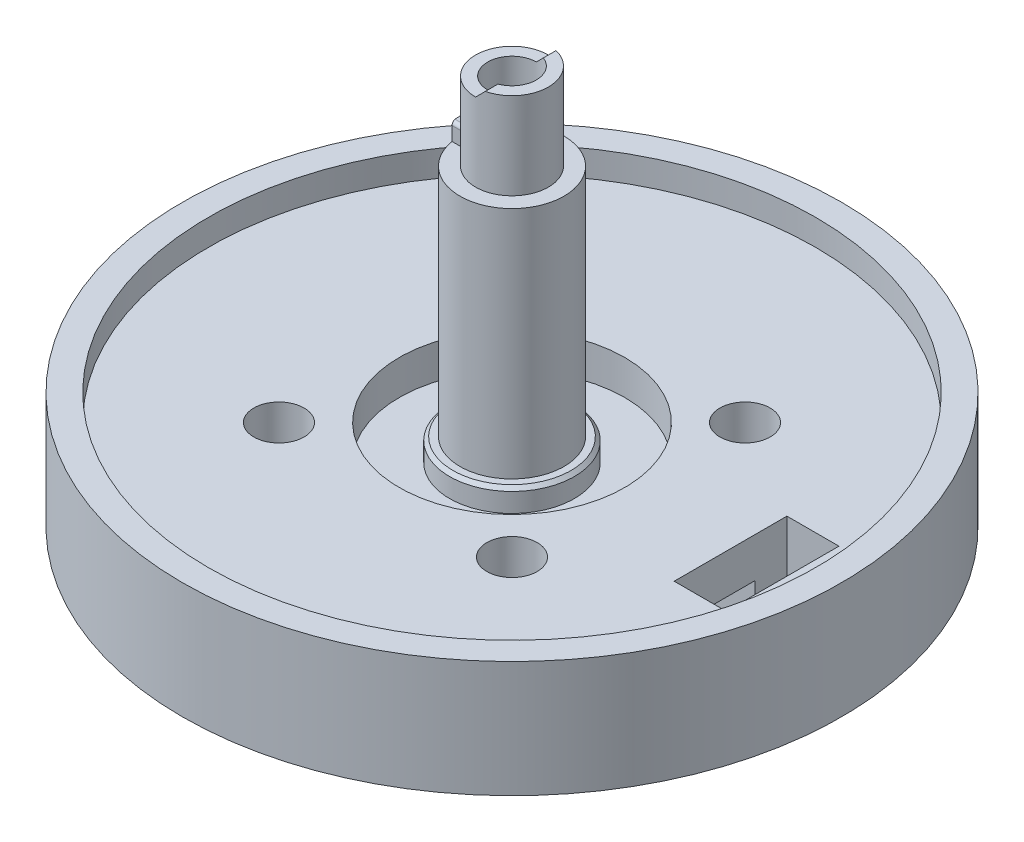
SolidWorks part; units mm, degrees
ref_plane "前视基准面" through (0, 0, 0) normal (0, 0, 1) x (1, 0, 0)
ref_plane "上视基准面" through (0, 0, 0) normal (0, 1, 0) x (1, 0, 0)
ref_plane "右视基准面" through (0, 0, 0) normal (1, 0, 0) x (0, 0, -1)
sketch "草图1" plane through (0, 0, 0) normal (0, 0, 1) x (1, 0, 0)
  line L0 (0, 0) -> (0, 22.2201) construction
  line L1 (-3, 12.8) -> (-2.1, 12.8)
  line L2 (-2.1, 12.8) -> (-2.1, 17.8)
  line L3 (-2.1, 17.8) -> (-1.4, 17.8)
  line L4 (-1.4, 17.8) -> (-1.4, -2.6859)
  line L6 (-3, -0.7) -> (-3, 12.8)
  line L7 (-19, 1.5) -> (-17.5, 1.5)
  line L8 (-17.5, 1.5) -> (-17.5, 0)
  line L9 (-17.5, 0) -> (-6.5, 0)
  line L10 (-6.5, 0) -> (-6.5, -2)
  line L13 (-19, 1.5) -> (-19, -5.2)
  line L14 (-19, -5.2) -> (-1.4, -5.2)
  line L15 (-1.4, -5.2) -> (-1.4, -2.6859)
  line L16 (-21.0007, 0) -> (21.0007, 0) construction
  line L18 (0, 0) -> (0, -7.9329) construction
  line L19 (-3, -0.7) -> (-3.6, -0.7)
  line L20 (-3.6, -0.7) -> (-3.6, -2)
  line L21 (-3.6, -2) -> (-6.5, -2)
  point P19 (0, 0)
  point P24 (-2.55, 12.8)
  dimension "D1" = 6
  dimension "D2" = 2.8
  dimension "D3" = 5
  dimension "D4" = 35
  dimension "D5" = 13
  dimension "D6" = 2
  dimension "D7" = 5.2
  dimension "D8" = 1.5
  dimension "D9" = 0.7
  dimension "D10" = 12.8
  dimension "D11" = 1.5
  dimension "D12" = 1.3
  dimension "D13" = 7.2
revolve "旋转3" add sketch "草图1" angle 360 about L0
sketch "草图3" plane through (0, 17.8, 0) normal (0, 1, 0) x (1, 0, 0)
  line L0 (0, 0) -> (-3.9693, 0) construction
  line L2 (-3.2821, 0.5) -> (-1, 0.5)
  line L3 (-3.2821, 0.5) -> (-3.2821, -0.5)
  line L4 (-3.2821, -0.5) -> (-1, -0.5)
  line L5 (-1, 0.5) -> (-1, -0.5)
  circle A1 centre (0, 0) radius 3
  circle A2 centre (0, 0) radius 3
  circle M6 centre (0, 0) radius 2.1
  dimension "D1" = 1
  dimension "D2" = 2.2821
  dimension "D3" = 1
  dimension "D4" = 0
extrude "凸台-拉伸1" add sketch "草图3" along normal blind 1 from surface contours L0 L2 A2 M6 | L0 A2 L4 M6 region at (-2.5329, 17.8, 0.2508) region at (-2.5329, 17.8, -0.2508) starting at face at (0, 12.8, -3)
fillet "圆角1" radius 0.2 2 edges at (-2.4988, 13.8, 0.5) (-2.4988, 13.8, -0.5)
sketch "草图4" plane through (0, -5.2, 0) normal (0, -1, 0) x (1, 0, 0)
  line L0 (0, 0) -> (21.9958, 0) construction
  line L1 (12.6, -3.25) -> (15.6, -3.25)
  line L2 (12.6, -3.25) -> (12.6, 3.25)
  line L3 (12.6, 3.25) -> (15.6, 3.25)
  line L4 (15.6, -3.25) -> (15.6, 3.25)
  dimension "D1" = 3
  dimension "D2" = 6.5
  dimension "D3" = 12.6
extrude "切除-拉伸1" cut sketch "草图4" against normal up to next
sketch "草图6" plane through (0, -5.2, 0) normal (0, -1, 0) x (1, 0, 0)
  line L0 (-23.0962, 0) -> (23.0962, 0) construction
  line L1 (6.7175, 6.7175) -> (-6.7175, -6.7175) construction
  line L3 (0, 26.4551) -> (0, -26.4551) construction
  point P4 (0, 0)
  point P5 (0, 0)
  point P8 (-6.7175, 6.7175)
  point P9 (0, 0)
  point P10 (-6.7175, -6.7175)
  point P11 (6.7175, -6.7175)
  point P12 (6.7175, 6.7175)
  point P16 (0, 0)
  dimension "D1" = 19
  dimension "D2" = 45
hole_wizard "Ø2.9 (2.9) 直径孔1" positions "草图7" profile "草图8" hole size "Ø2.9" standard "GB" end condition up to next
sketch "草图7" plane through (0, -5.2, 0) normal (0, -1, 0) x (-1, 0, 0)
  point P0 (-6.7175, 6.7175)
  point P3 (6.7175, 6.7175)
  point P6 (6.7175, -6.7175)
  point P9 (-6.7175, -6.7175)
sketch "草图8" plane through (6.7175, -5.2, -6.7175) normal (1, 0, 0) x (0, 0, -1)
  line L0 (0, 0) -> (0, 5.2)
  line L1 (0, 5.2) -> (1.45, 5.2)
  line L2 (1.45, 5.2) -> (1.45, 0)
  line L5 (1.45, 0) -> (0, 0)
  line L11 (0, -6.35) -> (0, 107.95) construction
  dimension "通孔孔直径" = 2.9
  dimension "通孔孔深度" = 5.2
sketch "草图9" plane through (0, -5.2, 0) normal (0, -1, 0) x (1, 0, 0)
  line L1 (-3.25, 2.75) -> (3.25, 2.75)
  line L2 (-3.25, 2.75) -> (-3.25, -2.75)
  line L3 (-3.25, -2.75) -> (3.25, -2.75)
  line L4 (3.25, 2.75) -> (3.25, -2.75)
  line L6 (-23.0962, 0) -> (23.0962, 0) construction
  line L7 (0, 26.4551) -> (0, -26.4551) construction
  line L8 (-23.0962, 0) -> (23.0962, 0) construction
  line L9 (0, 26.4551) -> (0, -26.4551) construction
  dimension "D1" = 6.5
  dimension "D2" = 5.5
extrude "切除-拉伸2" cut sketch "草图9" against normal blind 1.9
sketch "草图10" plane through (0, -5.2, 0) normal (0, -1, 0) x (1, 0, 0)
  line L0 (-23.0962, 0) -> (23.0962, 0) construction
  line L1 (-23.0962, 0) -> (23.0962, 0) construction
  line L2 (12.6, 3.25) -> (12.6, -3.25) construction
  line L3 (0, 1.4) -> (12.6, 1.4)
  line L4 (0, 1.4) -> (0, -1.4)
  line L5 (0, -1.4) -> (12.6, -1.4)
  line L6 (12.6, 1.4) -> (12.6, -1.4)
  circle A0 centre (0, 0) radius 1.4 construction
  circle A3 centre (0, 0) radius 1.4 construction
extrude "切除-拉伸3" cut sketch "草图10" against normal offset from surface (2.9 mm away) 1 up to face at (0, -3.3, 0) offset beyond the face yes
chamfer "倒角1" distance 1 angle 45 3 edges at (3.25, -3.3, -2.075) (3.25, -3.3, 2.075) (-3.25, -3.3, 0)
chamfer "倒角2" distance 0.2 angle 45 1 edges at (0, -0.7, -3.6)
sketch "草图11" plane through (0, 17.8, 0) normal (0, 1, 0) x (1, 0, 0)
  line L0 (0, -26.4551) -> (0, 26.4551) construction
  line L1 (0, 2.1) -> (-2.2966, 2.1)
  line L2 (0, 2.1) -> (0, -2.1)
  line L3 (0, -2.1) -> (-2.2966, -2.1)
  line L4 (-2.2966, 2.1) -> (-2.2966, -2.1)
  circle A0 centre (0, 0) radius 2.1 construction
extrude "切除-拉伸4" cut sketch "草图11" against normal blind 0.5
chamfer "倒角3" distance 0.5 angle 45 2 edges at (0, 17.8, 1.75) (0, 17.8, -1.75)
